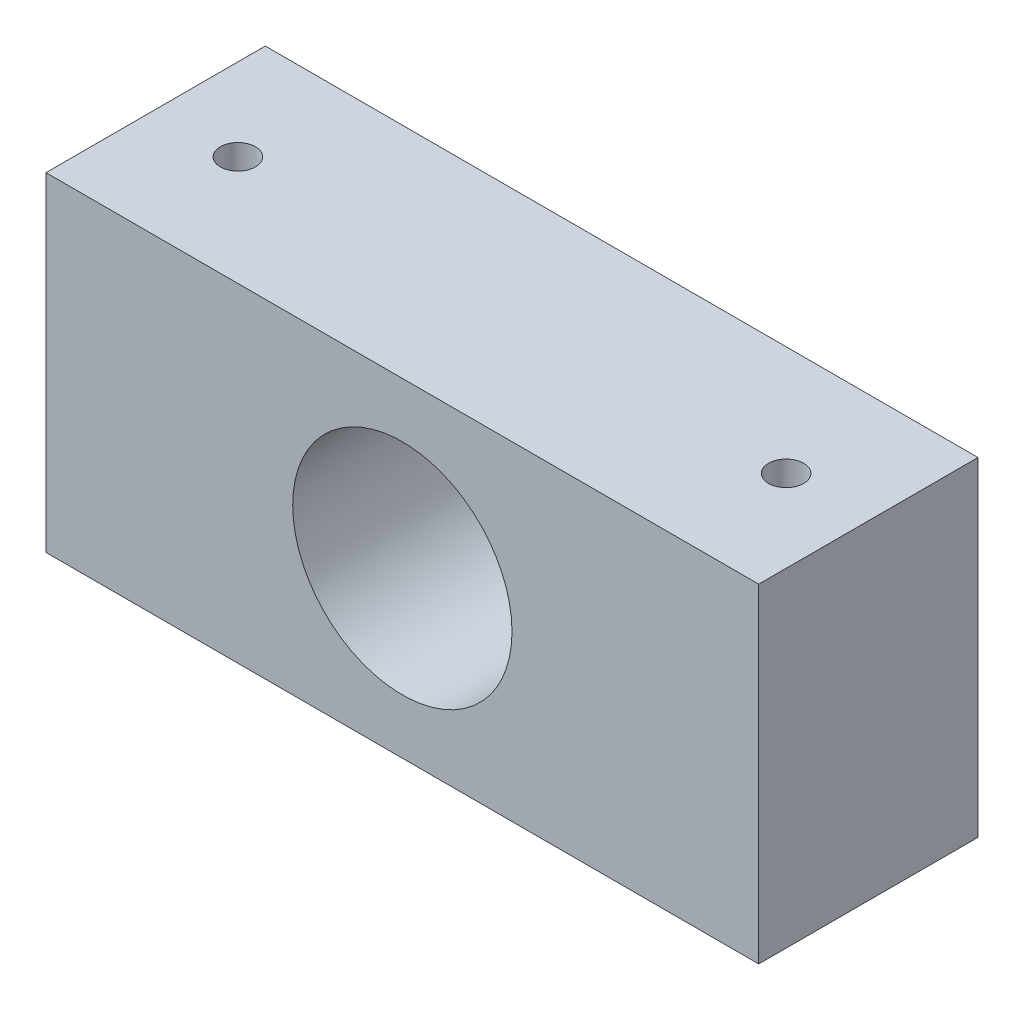
SolidWorks part; units mm, degrees
ref_plane "Front Plane" through (0, 0, 0) normal (0, 0, 1) x (1, 0, 0)
ref_plane "Top Plane" through (0, 0, 0) normal (0, 1, 0) x (1, 0, 0)
ref_plane "Right Plane" through (0, 0, 0) normal (1, 0, 0) x (0, 0, -1)
sketch "Sketch2" plane through (0, 0, 0) normal (0, 0, 1) x (1, 0, 0)
  line L0 (0, 30) -> (65, 0) construction
  line L1 (0, 0) -> (65, 0)
  line L2 (0, 0) -> (0, 30)
  line L3 (0, 30) -> (65, 30)
  line L4 (65, 0) -> (65, 30)
  circle A0 centre (32.5, 15) radius 10
  point P7 (0, 0)
  dimension "D3" = 20
  dimension "D1" = 30
  dimension "D2" = 65
extrude "Boss-Extrude1" add sketch "Sketch2" along normal blind 20
sketch "Sketch3" plane through (0, 0, 0) normal (0, 1, 0) x (1, 0, 0)
  line L0 (0, -10) -> (65, -10) construction
  line L1 (0, -20) -> (0, 0) construction
  line L2 (65, -20) -> (65, 0) construction
  line L3 (32.5, 0) -> (32.5, -20) construction
  line L4 (65, 0) -> (0, 0) construction
  line L5 (65, -20) -> (0, -20) construction
  circle A0 centre (7.5, -10) radius 1.6
  circle A1 centre (57.5, -10) radius 1.6
  point P10 (0, 0)
  dimension "D1" = 3.2
  dimension "D2" = 50
extrude "Cut-Extrude1" cut sketch "Sketch3" along normal through all both and the other way through all
